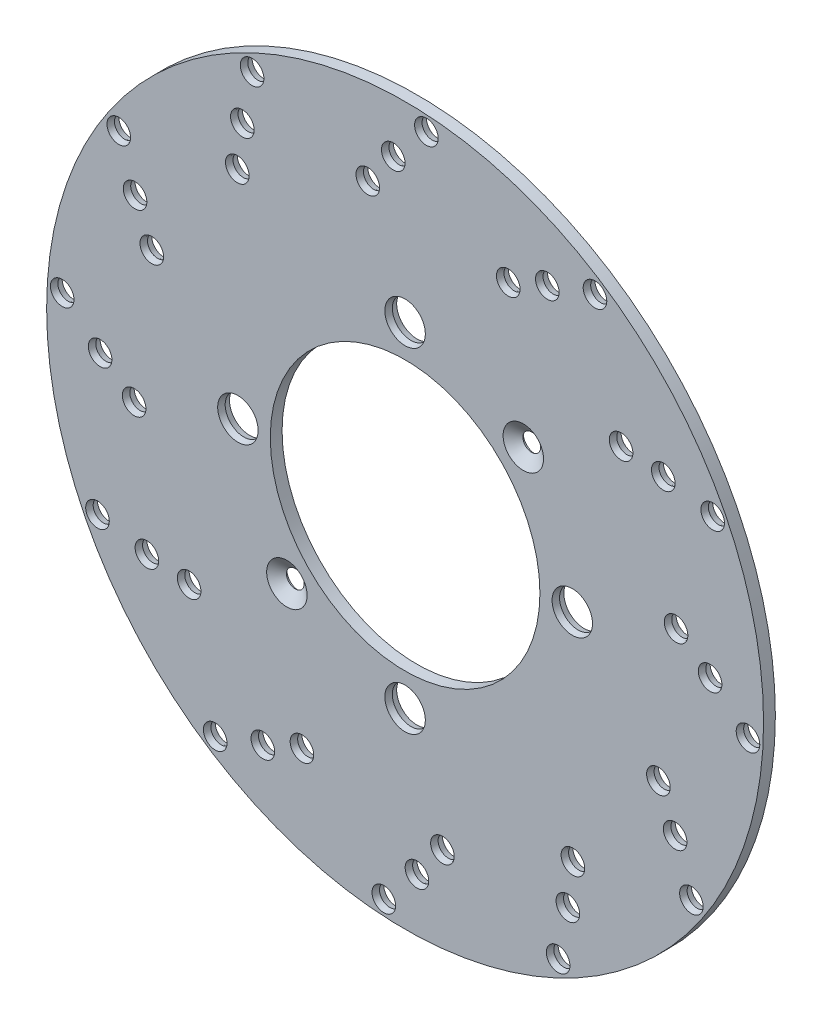
SolidWorks part; units mm, degrees
ref_plane "정면" through (0, 0, 0) normal (0, 0, 1) x (1, 0, 0)
ref_plane "윗면" through (0, 0, 0) normal (0, 1, 0) x (1, 0, 0)
ref_plane "우측면" through (0, 0, 0) normal (1, 0, 0) x (0, 0, -1)
sketch "스케치1" plane through (0, 0, 0) normal (0, 0, 1) x (1, 0, 0)
  circle A0 centre (0, 0) radius 106.35
  circle A1 centre (0, 0) radius 40
extrude "보스-돌출1" add sketch "스케치1" along normal blind 3.5
ref_plane "평면1" through (0, 0, 1.75) normal (0, 0, 1) x (1, 0, 0)
sketch "스케치2" plane through (0, 0, 3.5) normal (0, 0, 1) x (1, 0, 0)
  line L0 (-106.35, 0) -> (106.35, 0)
  line L1 (0, 106.35) -> (0, -106.35)
  line L2 (0, 40) -> (0, 49.6)
  line L3 (61.8866, 86.4891) -> (56.3327, 84.9433)
  line L4 (56.3327, 84.9433) -> (42.1992, 80.122)
  line L5 (42.1992, 80.122) -> (30.6017, 75.1508)
  circle A0 centre (0, 0) radius 106.35 construction
  circle A1 centre (0, 0) radius 40 construction
  circle A2 centre (0, 49.6) radius 6
  circle A3 centre (35.0725, 35.0725) radius 6
  circle A4 centre (49.6, 0) radius 6
  circle A6 centre (0, -49.6) radius 6
  circle A7 centre (-35.0725, -35.0725) radius 6
  circle A8 centre (-49.6, 0) radius 6
  circle A10 centre (-35.0725, 35.0725) radius 6 [skipped]
  circle A11 centre (35.0725, -35.0725) radius 6 [skipped]
  circle A12 centre (56.3327, 84.9433) radius 3.5
  circle A13 centre (42.1992, 80.122) radius 3.5
  circle A14 centre (30.6017, 75.1508) radius 3.5
  circle A15 centre (64.0772, 49.7817) radius 3.5
  circle A16 centre (91.2572, 45.3967) radius 3.5
  circle A17 centre (76.6066, 48.2881) radius 3.5
  circle A18 centre (80.3833, 11.0736) radius 3.5
  circle A19 centre (101.7294, -6.3139) radius 3.5
  circle A20 centre (90.4873, 3.5155) radius 3.5
  circle A21 centre (75.1508, -30.6017) radius 3.5
  circle A22 centre (84.9433, -56.3327) radius 3.5
  circle A23 centre (80.122, -42.1992) radius 3.5
  circle A24 centre (49.7817, -64.0772) radius 3.5
  circle A25 centre (45.3967, -91.2572) radius 3.5
  circle A26 centre (48.2881, -76.6066) radius 3.5
  circle A27 centre (11.0736, -80.3833) radius 3.5
  circle A28 centre (-6.3139, -101.7294) radius 3.5
  circle A29 centre (3.5155, -90.4873) radius 3.5
  circle A30 centre (-30.6017, -75.1508) radius 3.5
  circle A31 centre (-56.3327, -84.9433) radius 3.5
  circle A32 centre (-42.1992, -80.122) radius 3.5
  circle A33 centre (-64.0772, -49.7817) radius 3.5
  circle A34 centre (-91.2572, -45.3967) radius 3.5
  circle A35 centre (-76.6066, -48.2881) radius 3.5
  circle A36 centre (-80.3833, -11.0736) radius 3.5
  circle A37 centre (-101.7294, 6.3139) radius 3.5
  circle A38 centre (-90.4873, -3.5155) radius 3.5
  circle A39 centre (-75.1508, 30.6017) radius 3.5
  circle A40 centre (-84.9433, 56.3327) radius 3.5
  circle A41 centre (-80.122, 42.1992) radius 3.5
  circle A42 centre (-49.7817, 64.0772) radius 3.5
  circle A43 centre (-45.3967, 91.2572) radius 3.5
  circle A44 centre (-48.2881, 76.6066) radius 3.5
  circle A45 centre (-11.0736, 80.3833) radius 3.5
  circle A46 centre (6.3139, 101.7294) radius 3.5
  circle A47 centre (-3.5155, 90.4873) radius 3.5
  spline S0 degree 2 poles (-3.6591, 54.3551) (32.8363, 81.9222) (76.2582, 89.6351) knots 0 0 0 1 1 1
  point P28 (0, 0)
  point P37 (0, 0)
  point P106 (0, 0)
  dimension "D1" = 8
  dimension "D2" = 12
  dimension "D3" = 12
  dimension "D4" = 49.6
extrude "컷-돌출1" cut sketch "스케치2" against normal blind 1.75 draft 15 from surface contours A43 | A44 | A42 | A40 | A41 | A39 | A37 | A38 | A36 | A34 | A35 | A33 | A31 | A32 | A30 | A28 | A29 | A27 | A25 | A26 | A24 | A22 | A23 | A21 | A19 | A20 | A18 | A16 | A17 | A15 | A14 | A13 | A12 | A46 | A47 | A45 starting at face at (106.35, 0, 3.5)
extrude "컷-돌출2" cut sketch "스케치2<6>" along normal blind 1.75 draft 15 from surface contours A22 | A23 | A21 | A19 | A20 | A18 | A16 | A17 | A15 | A12 | A13 | A14 | A46 | A47 | A45 | A43 | A44 | A42 | A40 | A41 | A39 | A37 | A38 | A36 | A34 | A35 | A33 | A31 | A32 | A30 | A28 | A29 | A27 | A25 | A26 | A24 starting at face at (106.35, 0, 0)
sketch "스케치2<6>" plane through (0, 0, 3.5) normal (0, 0, 1) x (1, 0, 0) same geometry as "스케치2"
extrude "컷-돌출3" cut sketch "스케치2<7>" against normal blind 1.75 draft 15 from surface contours A8 | A6 | A4 | A2 starting at face at (-44.7881, 76.6066, 3.5)
sketch "스케치2<7>" plane through (0, 0, 3.5) normal (0, 0, 1) x (1, 0, 0) same geometry as "스케치2"
extrude "컷-돌출4" cut sketch "스케치2<8>" along normal blind 1.75 draft 15 from surface contours A4 | A6 | A8 | A2 starting at face at (-46.2817, 64.0772, 0)
sketch "스케치2<8>" plane through (0, 0, 3.5) normal (0, 0, 1) x (1, 0, 0) same geometry as "스케치2"
sketch "스케치6" plane through (0, 0, 0) normal (0, 0, -1) x (-1, 0, 0)
  circle A0 centre (-35.0725, 35.0725) radius 3.5
  circle A1 centre (35.0725, -35.0725) radius 3.5
extrude "컷-돌출5" cut sketch "스케치6" against normal blind 1
extrude "컷-돌출7" cut sketch "스케치2<14>" against normal blind 2.5 draft 53.5 contours A7
sketch "스케치2<14>" plane through (0, 0, 3.5) normal (0, 0, 1) x (1, 0, 0) same geometry as "스케치2"
extrude "컷-돌출9" cut sketch "스케치2<16>" against normal blind 2.5 draft 53.5 contours A3
sketch "스케치2<16>" plane through (0, 0, 3.5) normal (0, 0, 1) x (1, 0, 0) same geometry as "스케치2"
